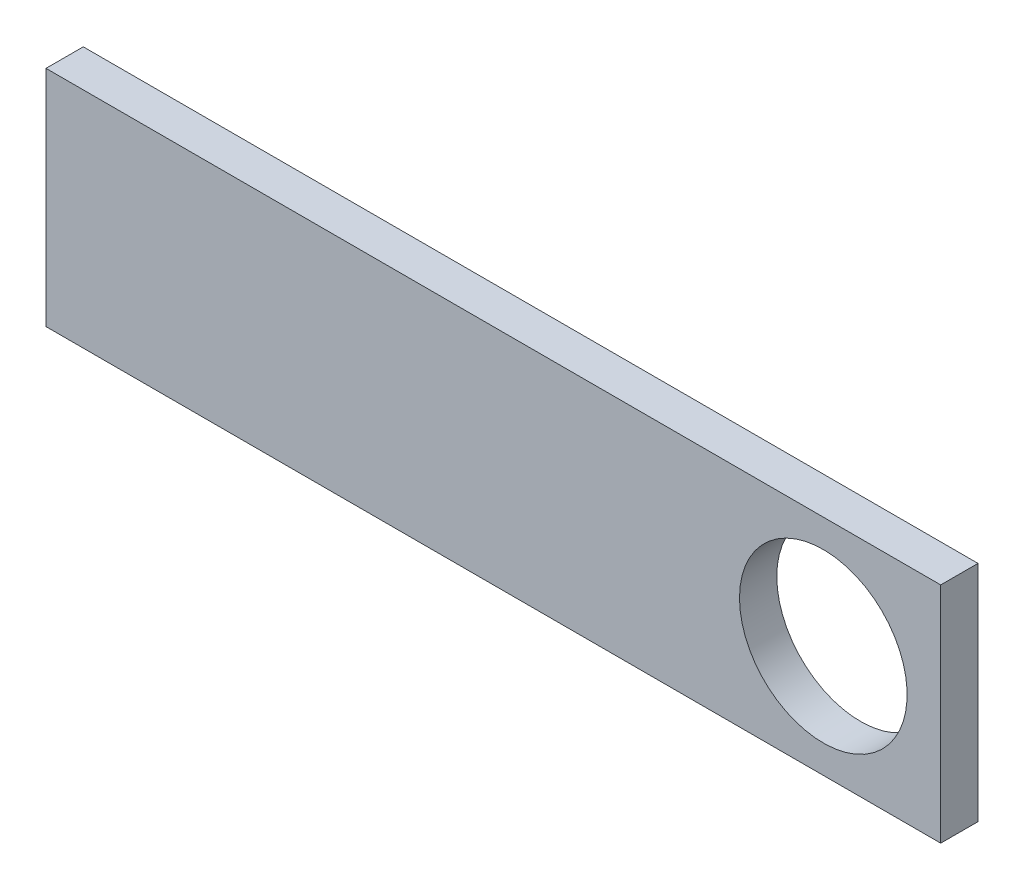
SolidWorks part; units mm, degrees
ref_plane "Front Plane" through (0, 0, 0) normal (0, 0, 1) x (1, 0, 0)
ref_plane "Top Plane" through (0, 0, 0) normal (0, 1, 0) x (1, 0, 0)
ref_plane "Right Plane" through (0, 0, 0) normal (1, 0, 0) x (0, 0, -1)
sketch "Sketch1" plane through (0, 0, 0) normal (0, 0, 1) x (1, 0, 0)
  line L1 (0, 0) -> (152.4, 0)
  line L2 (0, 0) -> (0, -38.1)
  line L3 (0, -38.1) -> (152.4, -38.1)
  line L4 (152.4, 0) -> (152.4, -38.1)
  dimension "D1" = 38.1
  dimension "D2" = 152.4
extrude "Boss-Extrude1" add sketch "Sketch1" along normal blind 6.35
sketch "Sketch2" plane through (0, 0, 0) normal (0, 0, -1) x (-1, 0, 0)
  line L0 (-152.4, -38.1) -> (-152.4, 0) construction
  circle A0 centre (-132.4, -19.05) radius 14.275
  point P5 (-152.4, -19.05)
  dimension "D1" = 28.55
  dimension "D2" = 20
extrude "Cut-Extrude1" cut sketch "Sketch2" against normal through all
